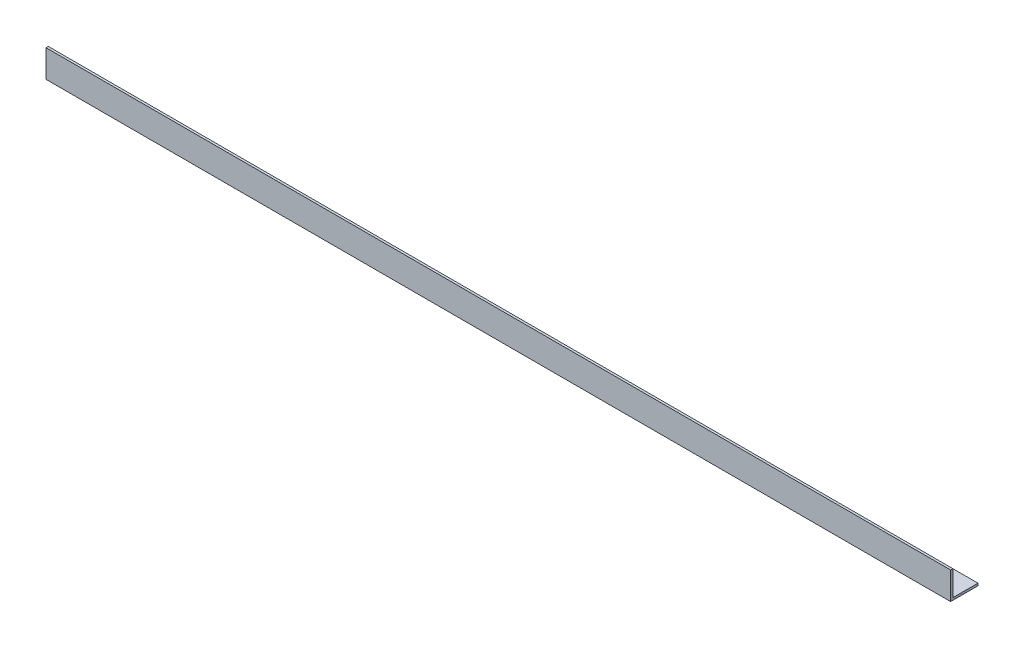
SolidWorks part; units mm, degrees
ref_plane "Front Plane" through (0, 0, 0) normal (0, 0, 1) x (1, 0, 0)
ref_plane "Top Plane" through (0, 0, 0) normal (0, 1, 0) x (1, 0, 0)
ref_plane "Right Plane" through (0, 0, 0) normal (1, 0, 0) x (0, 0, -1)
sketch "Sketch1" plane through (0, 0, 0) normal (1, 0, 0) x (0, 0, -1)
  line L0 (0, 19.05) -> (0, 0)
  line L1 (0, 0) -> (19.05, 0)
  dimension "D1" = 19.05
  dimension "D2" = 19.05
extrude "Extrude-Thin1" add sketch "Sketch1" along normal blind 628.65 thin thin type one direction reverse wall 1.5875
